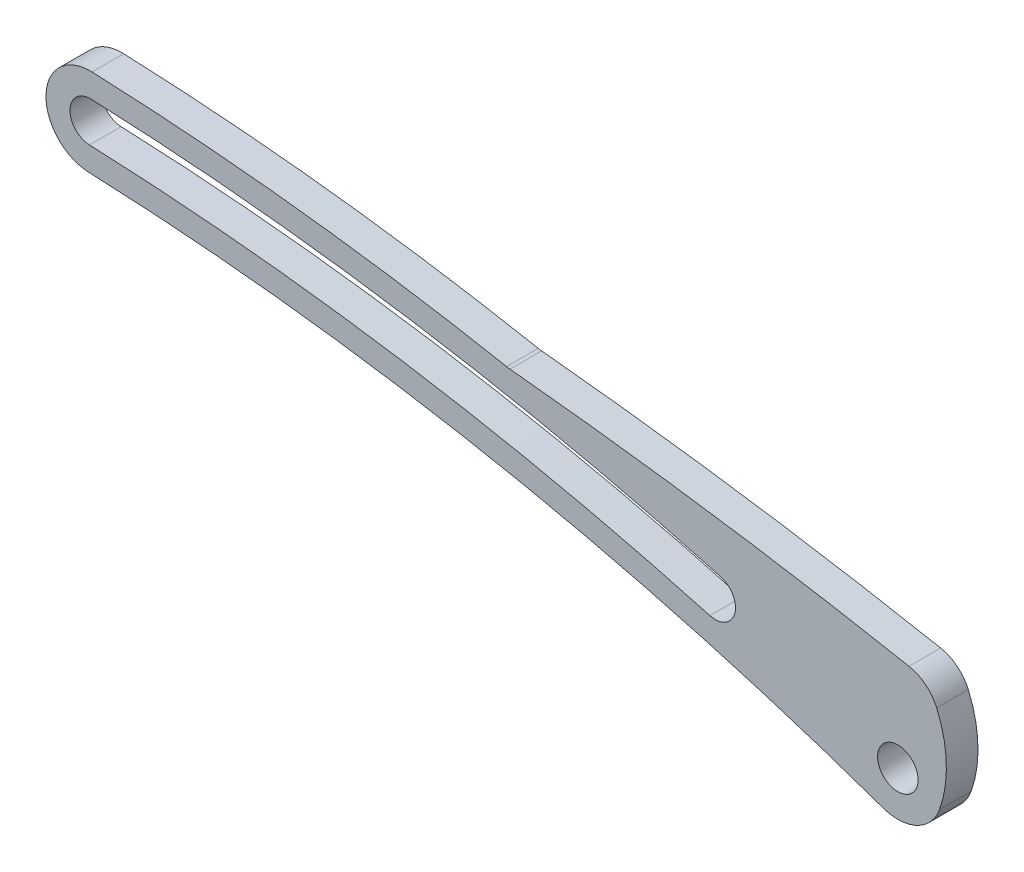
SolidWorks part; units mm, degrees
material "Thornel Mat VMA"
ref_plane "Front Plane" through (0, 0, 0) normal (0, 0, 1) x (1, 0, 0)
ref_plane "Top Plane" through (0, 0, 0) normal (0, 1, 0) x (1, 0, 0)
ref_plane "Right Plane" through (0, 0, 0) normal (1, 0, 0) x (0, 0, -1)
sketch "Sketch1" plane through (0, 0, 0) normal (0, 0, 1) x (1, 0, 0)
  circle A0 centre (-22.5, -7) radius 1.6
  circle A1 centre (-22.5, -7) radius 3.5
  arc A2 (-21.3284, -3.7019) -> (-86.1826, 8.8138) centre (-94.97, -211.0107) ccw
  arc A3 (-23.6716, -10.2981) -> (-86.4622, 1.8194) centre (-94.97, -211.0107) ccw
  arc A4 (-86.1826, 8.8138) -> (-86.4622, 1.8194) centre (-86.3224, 5.3166) ccw
  circle A5 centre (-86.3224, 5.3166) radius 1.6
  arc A6 (-86.2585, 6.9153) -> (-21.9644, -5.4923) centre (-94.97, -211.0107) cw
  arc A7 (-86.3864, 3.7179) -> (-23.0356, -8.5077) centre (-94.97, -211.0107) cw
  arc A9 (-36.4982, -0.8948) -> (-37.3561, -3.9777) centre (-36.9272, -2.4363) cw
  dimension "D1" = 3.2
  dimension "D2" = 7
  dimension "D3" = 220
  dimension "D4" = 65
  dimension "D5" = 50
extrude "Boss-Extrude1" add sketch "Sketch1" along normal blind 2.5 contours A7 A5 A6 A1 A2 A4 A3 | A7 A1 A6 A0 | A6 A9 A7 A1 | A1 A7 A0 A6 region at (-21.1123, -6.0203, 0) region at (-24.6599, -6.2444, 0) region at (-30.4727, -1.9212, 0) region at (-30.694, -4.2894, 0)
sketch "Sketch2" plane through (0, 0, 0) normal (0, 0, -1) x (-1, 0, 0)
  arc A0 (53.2832, 5.0037) -> (20.2407, 0.1564) centre (87.505, -343.3192) ccw
  arc A1 (86.1826, 8.8138) -> (21.3284, -3.7019) centre (94.97, -211.0107) ccw construction
  arc A2 (20.2407, 0.1564) -> (19.2019, -8.1716) centre (28.0125, -5.0418) ccw
  arc A3 (21.3284, -3.7019) -> (23.6716, -10.2981) centre (22.5, -7) ccw construction
  arc A4 (53.2832, 5.0037) -> (21.3284, -3.7019) centre (94.97, -211.0107) ccw
  arc A5 (21.3284, -3.7019) -> (19.2019, -8.1716) centre (22.5, -7) ccw
  point P8 (22.9538, 0.7312)
  point P12 (48.5775, 4.0422)
  point P13 (23.418, 1.0406)
  point P14 (20.1506, 0)
  point P15 (19.2019, -8.1716)
  point P16 (53.2832, 5.0037)
  dimension "D2" = 9.35
  dimension "D3" = 350
  dimension "D1" = 224
extrude "Boss-Extrude2" add sketch "Sketch2" against normal blind 2.5
fillet "Fillet1" radius 3 2 edges at (-53.2832, 5.0037, 1.25) (-20.2407, 0.1564, 1.25)
